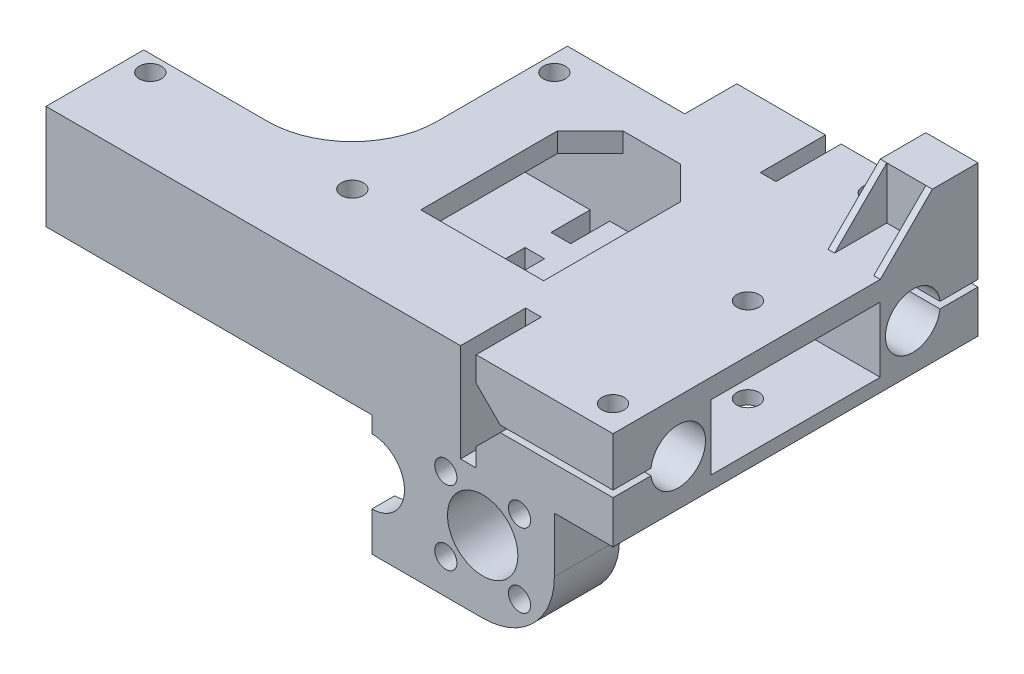
SolidWorks part; units mm, degrees
ref_plane "前视基准面" through (0, 0, 0) normal (0, 0, 1) x (1, 0, 0)
ref_plane "上视基准面" through (0, 0, 0) normal (0, 1, 0) x (1, 0, 0)
ref_plane "右视基准面" through (0, 0, 0) normal (1, 0, 0) x (0, 0, -1)
sketch "草图1" plane through (0, 0, 0) normal (0, 0, 1) x (1, 0, 0)
  line L0 (-21, 21) -> (21, -21) construction
  line L1 (-21, -21) -> (21, -21) construction
  line L2 (-21, -21) -> (-21, 21) construction
  line L3 (-21, 21) -> (21, 21) construction
  line L4 (-1001.4085, 24) -> (48998.5915, 24) construction
  line L5 (21, -21) -> (21, 21) construction
  line L6 (21, 21) -> (-21, -21) construction
  line L7 (11, 0) -> (11, 8.4569)
  line L8 (11, 8.4569) -> (21, 8.4569)
  line L9 (21, 8.4569) -> (21, 23.5)
  line L10 (21, 23.5) -> (-67, 23.5)
  line L11 (-67, 23.5) -> (-67, 7.5)
  line L12 (-67, 7.5) -> (-17, 7.5)
  line L13 (0, -11) -> (-17, -11)
  line L14 (-17, 7.5) -> (-17, 11)
  line L15 (-17, -11) -> (-17, 7.5)
  line L16 (11, 8.4569) -> (-4.5798, 8.4569)
  line L17 (21, 23.5) -> (28, 23.5)
  line L18 (21, 23.5) -> (21, 20.5)
  line L19 (21, 20.5) -> (28, 20.5)
  line L20 (28, 23.5) -> (28, 20.5)
  line L21 (21, 8.4569) -> (28, 8.4569)
  line L22 (21, 8.4569) -> (21, 10.5)
  line L23 (21, 10.5) -> (28, 10.5)
  line L24 (28, 8.4569) -> (28, 10.5)
  line L25 (12, 31.5) -> (20, 31.5)
  line L26 (12, 31.5) -> (12, 23.5)
  line L27 (12, 23.5) -> (21, 23.5)
  line L28 (20, 23.5) -> (20, 31.5)
  line L29 (-1067, 15.5) -> (48933, 15.5) construction
  circle A0 centre (0, 0) radius 5.4
  circle A1 centre (-17, 0) radius 4 construction
  circle A2 centre (-17, 0) radius 5
  circle A3 centre (-17, 0) radius 7.5
  circle A4 centre (-5.6569, 5.6569) radius 2.8 construction
  circle A5 centre (0, 0) radius 8 construction
  circle A6 centre (5.6569, 5.6569) radius 1.7
  circle A7 centre (5.6569, -5.6569) radius 1.7
  circle A8 centre (-5.6569, -5.6569) radius 1.7
  circle A9 centre (-5.6569, 5.6569) radius 1.7
  circle A10 centre (0, 0) radius 11
  circle A11 centre (-18.3322, 0) radius 11.0804
  circle A12 centre (16, 27.5) radius 1.5
  arc A13 (-4.5798, 8.4569) -> (-8.6437, 5.3766) centre (-5.6569, 5.6569) ccw
  point P0 (0, 0)
  point P25 (0, 0)
  point P54 (-67, 15.5)
  dimension "D1" = 10
  dimension "D2" = 10.8
  dimension "D3" = 15
  dimension "D4" = 5.6
  dimension "D5" = 16
  dimension "D6" = 3.4
  dimension "D9" = 22
  dimension "D10" = 16
  dimension "D11" = 10
  dimension "D18" = 3
  dimension "D21" = 3
  dimension "D8" = 3
  dimension "D12" = 5
  dimension "D13" = 5
  dimension "D14" = 7
  dimension "D15" = 50
  dimension "D16" = 8
  dimension "D17" = 8
  dimension "D19" = 4
  dimension "D20" = 4
  dimension "D22" = 1
  dimension "D7" = 4
extrude "凸台-拉伸1" add sketch "草图1" along normal blind 10 contours A11 A10 A0 A6 A7 A8 A9 | A10 A11 A3 | A10 A11 L14 A3 | L15 A11 A10 A3 | A11 L13 A10 | A11 A10 L7 L8 L9 L10 L11 L12 | L14 A11 L12 | L20 L17 L9 L19 | L21 L24 L23 L9 | A10 A11 | A10 L7 | A13 L16 A10 region at (9.8589, 6.4264, 0) region at (7.5793, -7.5793, 0) region at (-24.1727, 15.9599, 0) region at (-9.0499, -9.6181, 0) region at (0.0512, 9.4935, 0) region at (24.5, 9.4784, 0) region at (-13.2656, -7.8418, 0) region at (-8.7791, 0, 0) region at (-8.6998, 6.3406, 0) region at (-20.7478, 9.0153, 0) region at (-13.2656, 7.8418, 0) region at (24.5, 22, 0)
extrude "凸台-拉伸2" add sketch "草图1<6>" against normal blind 10 contours A11 A10 L16 L8 L9 L10 L11 L12 | L14 A11 L12 | A10 A11 L14 A3 | A10 A11 A3 | L15 A11 A10 A3 | A13 L16 A10 | A13 A10 A11 | L21 L24 L23 L9 | L18 L19 L20 L17 region at (-24.1727, 15.9599, 0) region at (0.0512, 9.4935, 0) region at (24.5, 9.4784, 0) region at (-13.2656, -7.8418, 0) region at (-8.7791, 0, 0) region at (-8.6998, 6.3406, 0) region at (-20.7478, 9.0153, 0) region at (-13.2656, 7.8418, 0)
sketch "草图1<6>" plane through (0, 0, 0) normal (0, 0, 1) x (1, 0, 0) same geometry as "草图1"
sketch "草图3" plane through (0, 0, 0) normal (0, 0, -1) x (-1, 0, 0)
  line L0 (0, 0) -> (5.6569, 5.6569) construction
  line L1 (7.9196, 3.3941) -> (8.7478, 6.4851)
  line L2 (8.7478, 6.4851) -> (6.4851, 8.7478)
  line L3 (6.4851, 8.7478) -> (3.3941, 7.9196)
  line L4 (3.3941, 7.9196) -> (2.5659, 4.8286)
  line L5 (2.5659, 4.8286) -> (4.8286, 2.5659)
  line L6 (4.8286, 2.5659) -> (7.9196, 3.3941)
  line L8 (-2.5659, 4.8286) -> (-3.3941, 7.9196)
  line L9 (-3.3941, 7.9196) -> (-6.4851, 8.7478)
  line L10 (-6.4851, 8.7478) -> (-8.7478, 6.4851)
  line L11 (-8.7478, 6.4851) -> (-7.9196, 3.3941)
  line L12 (-7.9196, 3.3941) -> (-4.8286, 2.5659)
  line L13 (-4.8286, 2.5659) -> (-2.5659, 4.8286)
  line L14 (-3.3941, -7.9196) -> (-2.5659, -4.8286)
  line L15 (-2.5659, -4.8286) -> (-4.8286, -2.5659)
  line L16 (-4.8286, -2.5659) -> (-7.9196, -3.3941)
  line L17 (-7.9196, -3.3941) -> (-8.7478, -6.4851)
  line L18 (-8.7478, -6.4851) -> (-6.4851, -8.7478)
  line L19 (-6.4851, -8.7478) -> (-3.3941, -7.9196)
  line L20 (2.5659, -4.8286) -> (3.3941, -7.9196)
  line L21 (3.3941, -7.9196) -> (6.4851, -8.7478)
  line L22 (6.4851, -8.7478) -> (8.7478, -6.4851)
  line L23 (8.7478, -6.4851) -> (7.9196, -3.3941)
  line L24 (7.9196, -3.3941) -> (4.8286, -2.5659)
  line L25 (4.8286, -2.5659) -> (2.5659, -4.8286)
  circle A0 centre (5.6569, 5.6569) radius 2.7713 construction
  circle A2 centre (-5.6569, 5.6569) radius 2.7713 construction
  circle A3 centre (-5.6569, -5.6569) radius 2.7713 construction
  circle A4 centre (5.6569, -5.6569) radius 2.7713 construction
  dimension "D1" = 3.2
  dimension "D2" = 3.2
  dimension "D3" = 3.2
  dimension "D4" = 3.2
extrude "切除-拉伸1" cut sketch "草图3" against normal blind 2
extrude "凸台-拉伸3" add sketch "草图1<7>" against normal blind 36 from offset 10 contours A11 A10 L16 L8 L9 L10 L11 L12 | L14 A11 L12 | A10 A11 L14 A3 | A10 A11 A3 | L15 A11 A10 A3 | A13 L16 A10 | A13 A10 A11 region at (-24.1727, 15.9599, 0) region at (0.0512, 9.4935, 0) region at (-13.2656, -7.8418, 0) region at (-8.7791, 0, 0) region at (-8.6998, 6.3406, 0) region at (-20.7478, 9.0153, 0) region at (-13.2656, 7.8418, 0) offset against normal yes
sketch "草图1<7>" plane through (0, 0, 0) normal (0, 0, 1) x (1, 0, 0) same geometry as "草图1"
extrude "凸台-拉伸4" add sketch "草图1<8>" along normal blind 3.5 from offset 6.5 contours A10 A3 L15 A2 | A3 A10 region at (-16.8361, -6.25, 0) region at (-10.2789, 0, 0)
sketch "草图1<8>" plane through (0, 0, 0) normal (0, 0, 1) x (1, 0, 0) same geometry as "草图1"
extrude "凸台-拉伸5" add sketch "草图1<9>" along normal blind 4 from offset 46 contours A10 A3 L15 A2 | A3 A10 region at (-16.8361, -6.25, 0) region at (-10.2789, 0, 0) offset against normal yes
sketch "草图1<9>" plane through (0, 0, 0) normal (0, 0, 1) x (1, 0, 0) same geometry as "草图1"
extrude "凸台-拉伸6" add sketch "草图1<10>" along normal blind 7 from offset 46 contours L25 L26 L10 A12 region at (16, 23.6131, 0) offset against normal yes
sketch "草图1<10>" plane through (0, 0, 0) normal (0, 0, 1) x (1, 0, 0) same geometry as "草图1"
sketch "草图4" plane through (20, 0, 0) normal (1, 0, 0) x (0, 0, -1)
  line L0 (39, 31.5) -> (31, 23.5)
  line L1 (46, 23.5) -> (10, 23.5) construction
rib "筋2" sketch "草图4" sketch "草图4" thickness 1 extrusion direction parallel to sketch draft on no parameters "D1"=1
sketch "草图5" plane through (12, 0, 0) normal (-1, 0, 0) x (0, 0, 1)
  line L0 (-39, 31.5) -> (-31, 23.5) construction
  line L1 (-39, 31.5) -> (-31, 23.5)
rib "筋3" sketch "草图5" sketch "草图5" thickness 1 extrusion direction parallel to sketch draft on no parameters "D1"=1
sketch "草图6" plane through (0, 0, -39) normal (0, 0, 1) x (1, 0, 0)
  circle A0 centre (16, 27.5) radius 1.5 construction
  circle A1 centre (16, 27.5) radius 1.5
extrude "凸台-拉伸7" add sketch "草图6" against normal blind 0.4
sketch "草图7" plane through (0, 23.5, 0) normal (0, 1, 0) x (1, 0, 0)
  line L0 (-987.3, 18) -> (49012.7, 18) construction
  line L1 (-8.6437, 5) -> (-5.6437, 5)
  line L2 (-8.6437, 5) -> (-8.6437, 11)
  line L3 (-8.6437, 11) -> (-5.6437, 11)
  line L4 (-5.6437, 5) -> (-5.6437, 11)
  line L5 (-5.6437, 31) -> (-5.6437, 25)
  line L6 (-8.6437, 15) -> (-5.6437, 15)
  line L7 (-8.6437, 15) -> (-8.6437, 21)
  line L8 (-8.6437, 21) -> (-5.6437, 21)
  line L9 (-5.6437, 15) -> (-5.6437, 21)
  line L10 (-8.6437, 31) -> (-8.6437, 25)
  line L11 (-8.6437, 31) -> (-5.6437, 31)
  line L12 (-8.6437, 25) -> (-5.6437, 25)
  line L13 (-8.6437, 46) -> (-8.6437, 0) construction
  line L14 (-24.5, 5) -> (-21.5, 5)
  line L15 (-24.5, 5) -> (-24.5, 11)
  line L16 (-24.5, 11) -> (-21.5, 11)
  line L17 (-21.5, 5) -> (-21.5, 11)
  line L18 (-21.5, 31) -> (-21.5, 25)
  line L19 (-24.5, 15) -> (-21.5, 15)
  line L20 (-24.5, 15) -> (-24.5, 21)
  line L21 (-24.5, 21) -> (-21.5, 21)
  line L22 (-21.5, 15) -> (-21.5, 21)
  line L23 (-24.5, 31) -> (-24.5, 25)
  line L24 (-24.5, 31) -> (-21.5, 31)
  line L25 (-24.5, 25) -> (-21.5, 25)
  line L26 (-24.5, -10) -> (-9.5, -10) construction
  line L27 (-24.5, 5) -> (-5.6437, 5)
  line L28 (-24.5, 5) -> (-24.5, 31)
  line L29 (-24.5, 31) -> (-5.6437, 31)
  line L30 (-5.6437, 5) -> (-5.6437, 31)
  line L31 (28, 0) -> (0, 0) construction
  line L32 (-27, 39) -> (-69, 39) construction
  line L33 (-27, 39) -> (-27, -3) construction
  line L34 (-27, -3) -> (-69, -3) construction
  line L35 (-69, 39) -> (-69, -3) construction
  line L36 (-27, 39) -> (-69, -3) construction
  line L37 (-27, -3) -> (-69, 39) construction
  line L38 (28, -10) -> (28, 10) construction
  line L39 (-17, 46) -> (-17, 38)
  line L40 (-48, 5) -> (-69, 5)
  line L41 (-35, 18) -> (-35, 38)
  line L42 (-69, 5) -> (-69, 46)
  line L43 (-69, 46) -> (-17, 46)
  line L44 (-67, 46) -> (-17, 46) construction
  line L45 (-17, 38) -> (-35, 38)
  line L46 (21, 46) -> (-4.5798, 46) construction
  line L47 (-1, 46) -> (-3.4, 46)
  line L48 (-1, 46) -> (-1, 36)
  line L49 (-1, 36) -> (-3.4, 36)
  line L50 (-3.4, 46) -> (-3.4, 36)
  line L51 (-1, -10) -> (-3.4, -10)
  line L52 (-1, -10) -> (-1, 0)
  line L53 (-3.4, -10) -> (-3.4, 0)
  line L54 (-1, 0) -> (-3.4, 0)
  circle A0 centre (12.7, 18) radius 1.7
  circle A1 centre (16, -6) radius 1.7
  circle A2 centre (8, 42) radius 1.7
  circle A3 centre (-48, 18) radius 13
  circle A4 centre (-32.5, 2.5) radius 1.7
  circle A5 centre (-63.5, 2.5) radius 1.7
  circle A6 centre (-63.5, 33.5) radius 1.7
  circle A7 centre (-32.5, 33.5) radius 1.7
  circle A8 centre (24.5, -5) radius 1.35
  circle A9 centre (24.5, 5) radius 1.35
  point P36 (-48, 18)
  point P59 (-48, 18)
  line M27 (12, 46) -> (-67, 46)
  line M28 (-67, 46) -> (-67, -10)
  line M29 (-67, -10) -> (28, -10)
  dimension "D1" = 3.4
  dimension "D9" = 3.4
  dimension "D12" = 3.4
  dimension "D18" = 26
  dimension "D19" = 3.4
  dimension "D22" = 2.7
  dimension "D2" = 18
  dimension "D3" = 12.7
  dimension "D4" = 3
  dimension "D5" = 6
  dimension "D6" = 6
  dimension "D8" = 24.5
  dimension "D10" = 42
  dimension "D11" = 8
  dimension "D13" = 6
  dimension "D14" = 16
  dimension "D16" = 42
  dimension "D17" = 15.5
  dimension "D21" = 15
  dimension "D23" = 10
  dimension "D24" = 24.5
  dimension "D25" = 4.5
  dimension "D26" = 2.4
  dimension "D27" = 1
  dimension "D28" = 18
  dimension "D29" = 8.6437
  dimension "D30" = 26
  dimension "D31" = 17
  dimension "D32" = 48
  dimension "D7" = 2
  dimension "D20" = 4
extrude "切除-拉伸2" cut sketch "草图7" against normal through all contours A3 L41 L40 A6 M27 M28 | A3 | A6 | A4 | A7 | A8 | A0 | A2 | A5 | A1 | A9 region at (-49.1293, 23.5, -33.3701) region at (-48, 23.5, -18) region at (12.7, 23.5, -18) region at (8, 23.5, -42) region at (-32.5, 23.5, -2.5) region at (-63.5, 23.5, -33.5) region at (-32.5, 23.5, -33.5) region at (24.5, 23.5, 5)
sketch "草图8" plane through (21, 0, 0) normal (1, 0, 0) x (0, 0, -1)
  line L0 (-1024.2568, 15.5) -> (48975.7432, 15.5) construction
  line L1 (-10, 10.5) -> (-10, 20.5) construction
  line L2 (18, -1011) -> (18, 48989) construction
  line L3 (0, 19.7) -> (0, 11.3)
  line L5 (5, 10.5) -> (31, 10.5)
  line L6 (5, 10.5) -> (5, 20.5)
  line L7 (5, 20.5) -> (31, 20.5)
  line L8 (31, 10.5) -> (31, 20.5)
  line L9 (5, 10.5) -> (31, 20.5) construction
  line L10 (5, 20.5) -> (31, 10.5) construction
  line L11 (-4.1701, 16) -> (-10, 16)
  line L12 (-4.1701, 15) -> (-10, 15)
  line L13 (40.1701, 15) -> (46, 15)
  line L14 (40.1701, 16) -> (46, 16)
  line L15 (36, 19.7) -> (36, 11.3)
  line L17 (-10, 16) -> (-10, 15)
  line L18 (46, 16) -> (46, 15)
  circle A0 centre (0, 15.5) radius 4.2
  circle A1 centre (36, 15.5) radius 4.2
  point P2 (18, 15.5)
  line M5 (-10, 20.5) -> (-10, 10.5)
  line M9 (46, 8.4569) -> (46, 23.5)
  dimension "D6" = 8.4
  dimension "D7" = 36
  dimension "D1" = 18
  dimension "D2" = 26
  dimension "D3" = 10
  dimension "D4" = 15.5
  dimension "D5" = 8
  dimension "D8" = 1
extrude "切除-拉伸3" cut sketch "草图8" against normal through all contours L5 L8 L7 L6 region at (21, 15.5, -18)
extrude "切除-拉伸4" cut sketch "草图8<3>" against normal blind 22 contours A1 L15 | L3 A0 region at (21, 15.5, -1.7825) region at (21, 15.5, -34.2175)
sketch "草图8<3>" plane through (21, 0, 0) normal (1, 0, 0) x (0, 0, -1) same geometry as "草图8"
extrude "切除-拉伸5" cut sketch "草图8<4>" against normal blind 24 contours A1 L15 | L14 A1 L13 M9 | L3 A0 | A0 L11 L12 M5 region at (21, 15.5, 1.7825) region at (21, 15.5, 7.095) region at (21, 15.5, -43.095) region at (21, 15.5, -37.7825)
sketch "草图8<4>" plane through (21, 0, 0) normal (1, 0, 0) x (0, 0, -1) same geometry as "草图8"
extrude "切除-拉伸9" cut sketch "草图7<4>" against normal blind 15.05 contours L52 L54 L53 M29 | L48 L49 L50 L47 region at (-2.2, 23.5, 5)
sketch "草图7<4>" plane through (0, 23.5, 0) normal (0, 1, 0) x (1, 0, 0) same geometry as "草图7"
chamfer "倒角1" distance 3.7 angle 45 4 edges at (-1, 16, -43.0851) (-1, 15, -43.0851) (-1, 16, 7.0851) (-1, 15, 7.0851)
extrude "切除-拉伸10" cut sketch "草图7<5>" against normal up to vertex (18.1234 mm away) contours L6 L9 L8 L7 | L10 L12 L5 L11 | L23 L25 L18 L24 | L19 L22 L21 L20 | L14 L17 L16 L15 | L4 L3 L2 L1 region at (-23, 23.5, -8) region at (-7.1437, 23.5, -18) region at (-23, 23.5, -18) region at (-7.1437, 23.5, -28) region at (-23, 23.5, -28) up to point (-8.6437, 5.3766, -46)
sketch "草图7<5>" plane through (0, 23.5, 0) normal (0, 1, 0) x (1, 0, 0) same geometry as "草图7"
extrude "切除-拉伸11" cut sketch "草图7<6>" against normal up to next contours L3 L30 L6 L7 L8 L12 L10 L29 L18 L25 L28 L21 L22 L19 L16 L17 L27 L2 region at (-15.0719, 23.5, -18)
sketch "草图7<6>" plane through (0, 23.5, 0) normal (0, 1, 0) x (1, 0, 0) same geometry as "草图7"
chamfer "倒角2" distance 5 2 edges at (-24.5, 22, -31) (-5.6437, 22, -31)
chamfer "倒角3" distance 2 distance2 2.5 1 edges at (-12, 0, -42) first distance on face at (-13.875, 0, -42)
sketch "草图9" plane through (0, 0, 10) normal (0, 0, 1) x (1, 0, 0)
  line L0 (20, 31.5) -> (20, 7.2174)
  line L1 (20, 7.2174) -> (31.3229, 7.2174)
  line L2 (31.3229, 7.2174) -> (31.3229, 31.5)
  line L3 (31.3229, 31.5) -> (20, 31.5)
extrude "切除-拉伸12" cut sketch "草图9" against normal through all
